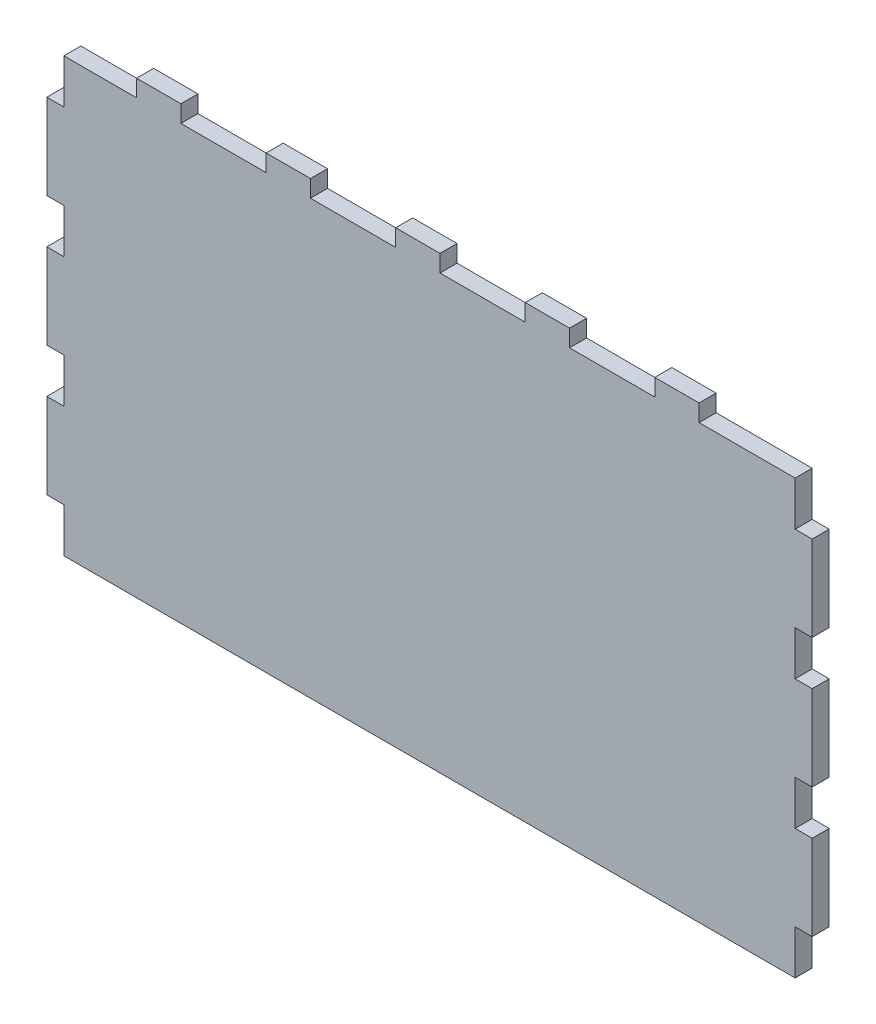
SolidWorks part; units mm, degrees
material "ENPH 253 Hardboard"
ref_plane "Front Plane" through (0, 0, 0) normal (0, 0, 1) x (1, 0, 0)
ref_plane "Top Plane" through (0, 0, 0) normal (0, 1, 0) x (1, 0, 0)
ref_plane "Right Plane" through (0, 0, 0) normal (1, 0, 0) x (0, 0, -1)
sketch "Sketch1" plane through (0, 0, 0) normal (0, 0, 1) x (1, 0, 0)
  line L1 (-67.35, 38.1) -> (67.35, 38.1)
  line L2 (-67.35, 38.1) -> (-67.35, -38.1)
  line L3 (-67.35, -38.1) -> (67.35, -38.1)
  line L4 (67.35, 38.1) -> (67.35, -38.1)
  line L5 (-67.35, 38.1) -> (67.35, -38.1) construction
  line L6 (-67.35, -38.1) -> (67.35, 38.1) construction
  point P0 (0, 0)
  dimension "D1" = 134.7
  dimension "D2" = 76.2
extrude "Boss-Extrude1" add sketch "Sketch1" along normal blind 3
sketch "Sketch2" plane through (0, 0, 3) normal (0, 0, 1) x (1, 0, 0)
  line L1 (-67.35, 38.1) -> (-64.35, 38.1)
  line L2 (-67.35, 38.1) -> (-67.35, 30.3)
  line L3 (-67.35, 30.3) -> (-64.35, 30.3)
  line L4 (-64.35, 38.1) -> (-64.35, 30.3)
  dimension "D1" = 3
  dimension "D2" = 7.8
extrude "Cut-Extrude1" cut sketch "Sketch2" against normal through all
pattern_linear "LPattern1" count 4 spacing 22.8 along (0, -1, 0) of "Cut-Extrude1"
mirror "Mirror4" about plane through (0, 0, 0) normal (1, 0, 0) of "LPattern1"
sketch "Sketch3" plane through (0, 38.1, 0) normal (0, 1, 0) x (1, 0, 0)
  line L0 (64.35, 0) -> (-64.35, 0) construction
  line L1 (-43.75, 0) -> (-51.55, 0)
  line L2 (-43.75, 0) -> (-43.75, -3)
  line L3 (-43.75, -3) -> (-51.55, -3)
  line L4 (-51.55, 0) -> (-51.55, -3)
  line L5 (64.35, -3) -> (-64.35, -3) construction
  line L6 (-64.35, 0) -> (-64.35, -3) construction
  dimension "D1" = 12.8
  dimension "D2" = 7.8
extrude "Boss-Extrude2" add sketch "Sketch3" along normal blind 3
pattern_linear "LPattern2" count 5 spacing 22.8 along (1, 0, 0) of "Boss-Extrude2"
